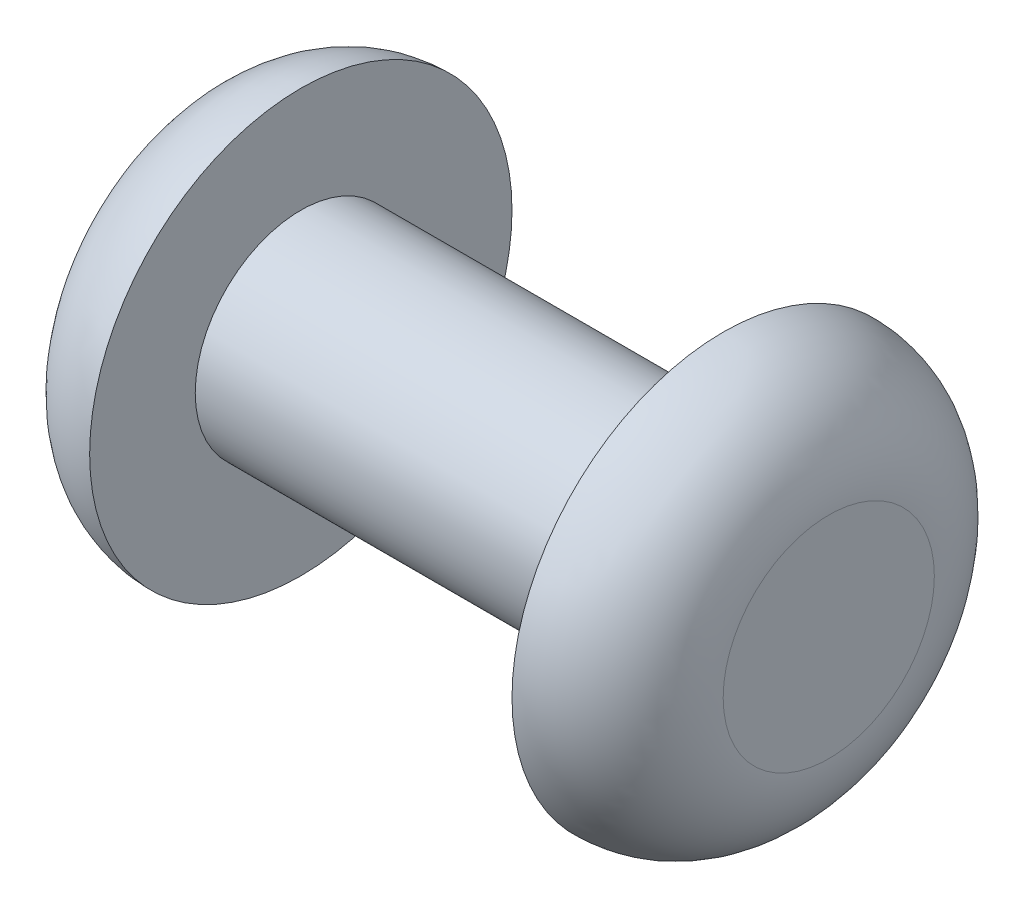
SolidWorks part; units mm, degrees
ref_plane "Front Plane" through (0, 0, 0) normal (0, 0, 1) x (1, 0, 0)
ref_plane "Top Plane" through (0, 0, 0) normal (0, 1, 0) x (1, 0, 0)
ref_plane "Right Plane" through (0, 0, 0) normal (1, 0, 0) x (0, 0, -1)
sketch "Sketch1" plane through (0, 0, 0) normal (1, 0, 0) x (0, 0, -1)
  circle A0 centre (0, 0) radius 10
  dimension "D1" = 20
extrude "Boss-Extrude1" add sketch "Sketch1" along normal blind 40
sketch "Sketch2" plane through (40, 0, 0) normal (1, 0, 0) x (0, 0, -1)
  circle A0 centre (0, 0) radius 20
  dimension "D1" = 40
extrude "Boss-Extrude2" add sketch "Sketch2" along normal blind 10
fillet "Fillet1" radius 10 1 edges at (50, 0, -20)
ref_plane "Plane1" through (20, 0, 0) normal (-1, 0, 0) x (0, 0, 1)
mirror "Mirror1" about plane through (20, 0, 0) normal (-1, 0, 0) of "Boss-Extrude2", "Fillet1"
